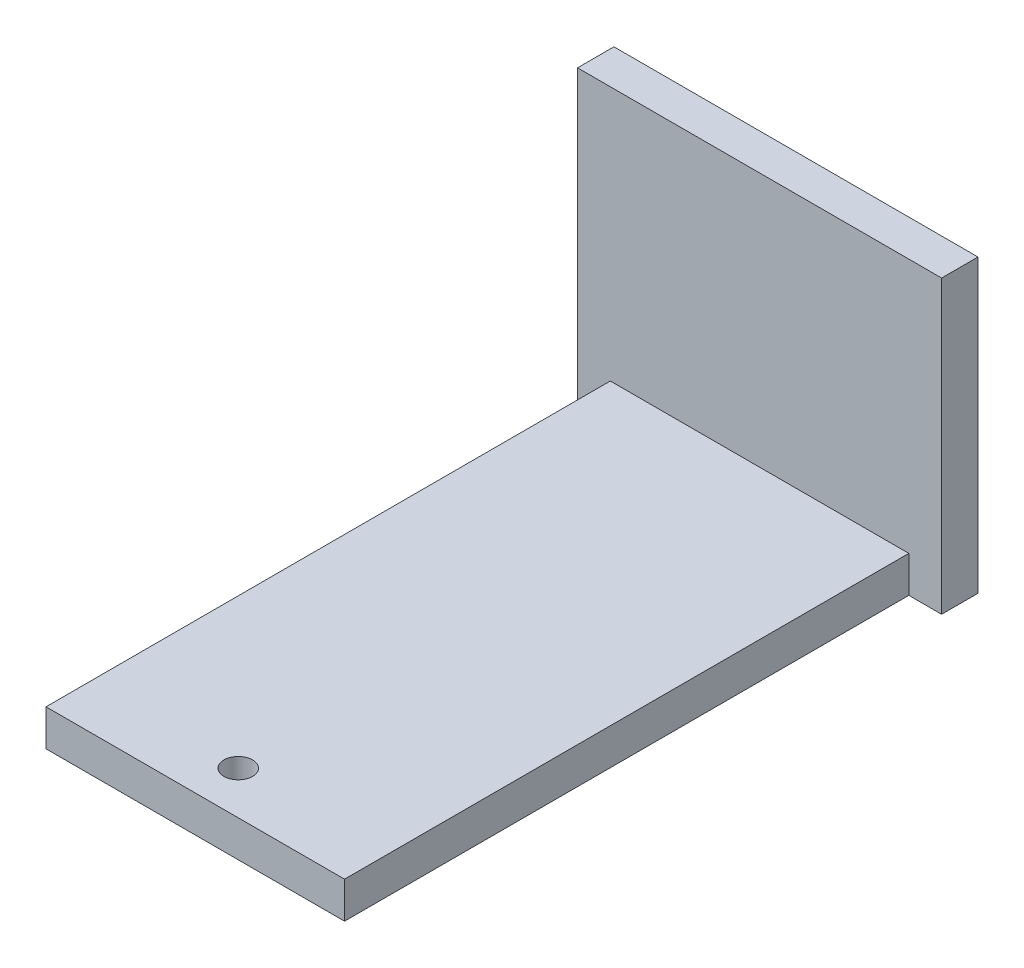
SolidWorks part; units mm, degrees
ref_plane "Front Plane" through (0, 0, 0) normal (0, 0, 1) x (1, 0, 0)
ref_plane "Top Plane" through (0, 0, 0) normal (0, 1, 0) x (1, 0, 0)
ref_plane "Right Plane" through (0, 0, 0) normal (1, 0, 0) x (0, 0, -1)
sketch "Sketch1" plane through (0, 0, 0) normal (0, 0, 1) x (1, 0, 0)
  line L1 (0, 0) -> (25.4, 0)
  line L2 (0, 0) -> (0, -25.4)
  line L3 (0, -25.4) -> (25.4, -25.4)
  line L4 (25.4, 0) -> (25.4, -25.4)
  dimension "D1" = 25.4
  dimension "D2" = 25.4
extrude "Boss-Extrude1" add sketch "Sketch1" along normal blind 2.54
ref_plane "Plane1" through (0, -19.05, 0) normal (0, 1, 0) x (1, 0, 0)
sketch "Sketch2" plane through (0, -19.05, 0) normal (0, 1, 0) x (1, 0, 0)
  line L0 (25.4, -2.54) -> (0, -2.54) construction
  line L1 (2.286, -41.91) -> (2.286, -2.54)
  line L2 (2.286, -2.54) -> (12.7, -2.54)
  line L3 (12.7, -2.54) -> (23.114, -2.54)
  line L4 (23.114, -2.54) -> (23.114, -41.91)
  line L5 (2.286, -41.91) -> (23.114, -41.91)
  point P13 (12.7, -2.54)
  dimension "D2" = 39.37
extrude "Boss-Extrude3" add sketch "Sketch2" along normal mid plane 2.54 contours L5 L2 L1 | L5 L4 L3 region at (12.7, -19.05, 22.225)
sketch "Sketch3" plane through (0, -17.78, 0) normal (0, 1, 0) x (1, 0, 0)
  line L0 (2.286, -41.91) -> (4.826, -41.91)
  line L1 (20.574, -41.91) -> (23.114, -41.91)
  arc A0 (2.286, -41.91) -> (23.114, -41.91) centre (12.7, -41.91) cw
  arc A1 (4.826, -41.91) -> (20.574, -41.91) centre (12.7, -41.91) cw
  dimension "D1" = 2.54
extrude "Boss-Extrude4" [suppressed] add sketch "Sketch3" against normal blind 0.635
mirror "Mirror1" [suppressed] about plane through (0, -19.05, 0) normal (0, 1, 0)
sketch "Sketch4" [suppressed] plane through (2.286, 0, 0) normal (-1, 0, 0) x (0, 0, 1)
  line L1 (2.54, -16.51) -> (35.56, -16.51)
  line L2 (2.54, -16.51) -> (2.54, -21.59)
  line L3 (2.54, -21.59) -> (35.56, -21.59)
  line L4 (35.56, -16.51) -> (35.56, -21.59)
extrude "Boss-Extrude5" [suppressed] add sketch "Sketch4" along normal up to surface (2.286 mm away) up to face at (0, -12.7, 1.27)
sketch "Sketch5" [suppressed] plane through (23.114, 0, 0) normal (1, 0, 0) x (0, 0, -1)
  line L1 (-35.56, -16.51) -> (-2.54, -16.51)
  line L2 (-35.56, -16.51) -> (-35.56, -21.59)
  line L3 (-35.56, -21.59) -> (-2.54, -21.59)
  line L4 (-2.54, -16.51) -> (-2.54, -21.59)
extrude "Boss-Extrude6" [suppressed] add sketch "Sketch5" along normal up to surface (2.286 mm away) up to face at (25.4, -12.7, 1.27)
sketch "Sketch6" plane through (0, 0, 41.91) normal (0, 0, 1) x (1, 0, 0)
  line L0 (25.4, -25.4) -> (25.4, 0) construction
  line L1 (0, -25.4) -> (25.4, -25.4)
  line L2 (0, -25.4) -> (0, -20.32)
  line L3 (0, -20.32) -> (25.4, -20.32)
  line L4 (25.4, -25.4) -> (25.4, -20.32)
  line L5 (2.286, -20.32) -> (23.114, -20.32) construction
extrude "Cut-Extrude1" cut sketch "Sketch6" against normal through all
sketch "Sketch7" plane through (0, -20.32, 0) normal (0, -1, 0) x (-1, 0, 0)
  line L0 (-23.114, -2.54) -> (-23.114, -41.91) construction
  line L1 (-2.286, -41.91) -> (-23.114, -41.91) construction
  circle A0 centre (-12.7, -38.91) radius 1
  dimension "D2" = 2
  dimension "D1" = 10.414
  dimension "D3" = 3
extrude "Cut-Extrude2" cut sketch "Sketch7" against normal through all
